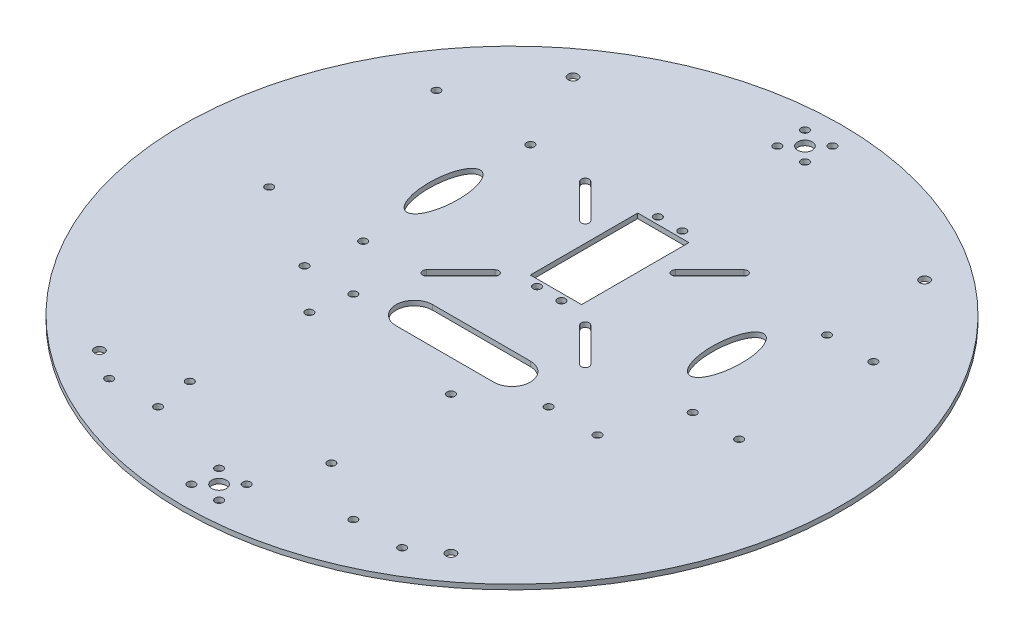
SolidWorks part; units mm, degrees
ref_plane "前视基准面" through (0, 0, 0) normal (0, 0, 1) x (1, 0, 0)
ref_plane "上视基准面" through (0, 0, 0) normal (0, 1, 0) x (1, 0, 0)
ref_plane "右视基准面" through (0, 0, 0) normal (1, 0, 0) x (0, 0, -1)
sketch "草图1" plane through (0, 0, 0) normal (0, 1, 0) x (1, 0, 0)
  line L0 (0, 135) -> (0, -135) construction
  line L1 (-80, 80) -> (80, 80) construction
  line L2 (-80, 80) -> (-80, -80) construction
  line L3 (-80, -80) -> (80, -80) construction
  line L4 (80, 80) -> (80, -80) construction
  line L5 (-80, 80) -> (80, -80) construction
  line L6 (-80, -80) -> (80, 80) construction
  line L7 (-135, 0) -> (135, 0) construction
  line L9 (-30, 60) -> (30, 60) construction
  line L10 (-30, 60) -> (-30, 0) construction
  line L11 (-30, 0) -> (30, 0) construction
  line L12 (30, 60) -> (30, 0) construction
  line L13 (-30, 60) -> (30, 0) construction
  line L14 (-30, 0) -> (30, 60) construction
  circle A0 centre (0, 0) radius 135
  point P17 (0, 0)
  point P19 (0, 30)
  dimension "D1" = 270
  dimension "D2" = 160
  dimension "D3" = 160
  dimension "D5" = 30
  dimension "D6" = 60
  dimension "D7" = 60
extrude "凸台-拉伸1" add sketch "草图1" along normal blind 2
sketch "云台安装孔" plane through (0, 2, 0) normal (0, 1, 0) x (1, 0, 0)
  line L0 (0, 135) -> (0, -135) construction
  line L1 (-135, 0) -> (135, 0) construction
  line L3 (-18.5, 48.5) -> (18.5, 48.5) construction
  line L4 (-18.5, 48.5) -> (-18.5, 11.5) construction
  line L5 (-18.5, 11.5) -> (18.5, 11.5) construction
  line L6 (18.5, 48.5) -> (18.5, 11.5) construction
  line L7 (-18.5, 48.5) -> (18.5, 11.5) construction
  line L8 (-18.5, 11.5) -> (18.5, 48.5) construction
  line L9 (-62.9961, -18.6558) -> (62.9961, -18.6558) construction
  line L10 (-62.9961, -18.6558) -> (-62.9961, -86.2012) construction
  line L11 (-62.9961, -86.2012) -> (62.9961, -86.2012) construction
  line L12 (62.9961, -18.6558) -> (62.9961, -86.2012) construction
  line L13 (-62.9961, -18.6558) -> (62.9961, -86.2012) construction
  line L14 (-62.9961, -86.2012) -> (62.9961, -18.6558) construction
  line L15 (-10.5, 62) -> (10.5, 62)
  line L16 (-10.5, 62) -> (-10.5, 18)
  line L17 (-10.5, 18) -> (10.5, 18)
  line L18 (10.5, 62) -> (10.5, 18)
  line L19 (-10.5, 62) -> (10.5, 18) construction
  line L20 (-10.5, 18) -> (10.5, 62) construction
  line L21 (-5, 64.75) -> (5, 64.75) construction
  line L22 (-5, 64.75) -> (-5, 15.25) construction
  line L23 (-5, 15.25) -> (5, 15.25) construction
  line L24 (5, 64.75) -> (5, 15.25) construction
  line L25 (-5, 64.75) -> (5, 15.25) construction
  line L26 (-5, 15.25) -> (5, 64.75) construction
  line L27 (-38.5, 68.5) -> (38.5, 68.5) construction
  line L28 (-38.5, 68.5) -> (-38.5, -8.5) construction
  line L29 (-38.5, -8.5) -> (38.5, -8.5) construction
  line L30 (38.5, 68.5) -> (38.5, -8.5) construction
  line L31 (-38.5, 68.5) -> (38.5, -8.5) construction
  line L32 (-38.5, -8.5) -> (38.5, 68.5) construction
  circle A0 centre (0, 0) radius 135 construction
  circle A1 centre (-5, 64.75) radius 1.6
  circle A2 centre (5, 64.75) radius 1.6
  circle A3 centre (-5, 15.25) radius 1.6
  circle A4 centre (5, 15.25) radius 1.6
  circle A5 centre (18.5, 48.5) radius 1.6
  circle A6 centre (18.5, 11.5) radius 1.6
  circle A7 centre (-18.5, 11.5) radius 1.6
  circle A8 centre (-18.5, 48.5) radius 1.6
  point P3 (0, 30)
  point P8 (0, 30)
  point P13 (0, -52.4285)
  point P18 (0, 40)
  point P23 (0, 40)
  point P50 (0, 30)
  dimension "D3" = 21
  dimension "D8" = 3.2
  dimension "D9" = 3.2
  dimension "D10" = 3.2
  dimension "D11" = 3.2
  dimension "D12" = 3.2
  dimension "D13" = 3.2
  dimension "D1" = 37
  dimension "D2" = 37
  dimension "D4" = 44
  dimension "D5" = 10
  dimension "D6" = 10
  dimension "D7" = 49.5
  dimension "D14" = 30
  dimension "D15" = 77
  dimension "D16" = 77
extrude "切除-拉伸1" cut sketch "云台安装孔" against normal blind 10
sketch "扩展板安装孔" plane through (0, 2, 0) normal (0, 1, 0) x (1, 0, 0)
  line L0 (0, 135) -> (0, -135) construction
  line L1 (15.5, -40.5) -> (15.5, -89.5) construction
  line L2 (-60, -25) -> (60, -25) construction
  line L3 (-60, -25) -> (-60, -105) construction
  line L4 (-60, -105) -> (60, -105) construction
  line L5 (60, -25) -> (60, -105) construction
  line L6 (-60, -25) -> (60, -105) construction
  line L7 (-60, -105) -> (60, -25) construction
  line L8 (-40, -25) -> (40, -25) construction
  line L9 (-40, -25) -> (-40, -105) construction
  line L10 (-40, -105) -> (40, -105) construction
  line L11 (40, -25) -> (40, -105) construction
  line L12 (-40, -25) -> (40, -105) construction
  line L13 (-40, -105) -> (40, -25) construction
  line L14 (-42.5, -40.5) -> (42.5, -40.5) construction
  line L15 (-42.5, -40.5) -> (-42.5, -89.5) construction
  line L16 (-42.5, -89.5) -> (42.5, -89.5) construction
  line L17 (42.5, -40.5) -> (42.5, -89.5) construction
  line L18 (-42.5, -40.5) -> (42.5, -89.5) construction
  line L19 (-42.5, -89.5) -> (42.5, -40.5) construction
  circle A0 centre (0, 0) radius 135 construction
  circle A1 centre (-60, -25) radius 1.6
  circle A2 centre (-40, -25) radius 1.6
  circle A3 centre (40, -25) radius 1.6
  circle A4 centre (60, -25) radius 1.6
  circle A5 centre (60, -105) radius 1.6
  circle A6 centre (40, -105) radius 1.6
  circle A7 centre (-40, -105) radius 1.6
  circle A8 centre (-60, -105) radius 1.6
  circle A9 centre (-42.5, -89.5) radius 1.6
  circle A12 centre (-42.5, -40.5) radius 1.6
  circle A13 centre (15.5, -40.5) radius 1.6
  circle A14 centre (15.5, -89.5) radius 1.6
  point P5 (0, -65)
  point P10 (0, -65)
  point P15 (0, -65)
  dimension "D7" = 65
  dimension "D1" = 120
  dimension "D2" = 80
  dimension "D3" = 80
  dimension "D4" = 85
  dimension "D5" = 49
  dimension "D6" = 58
extrude "切除-拉伸2" cut sketch "扩展板安装孔" against normal blind 10
sketch "草图4" plane through (0, 2, 0) normal (0, 1, 0) x (1, 0, 0)
  line L0 (0, 135) -> (0, -135) construction
  line L1 (-135, 0) -> (135, 0) construction
  line L2 (-20, -12.5) -> (20, -12.5)
  line L3 (-20, -12.5) -> (-20, -27.5) construction
  line L4 (-20, -27.5) -> (20, -27.5)
  line L5 (20, -12.5) -> (20, -27.5) construction
  line L6 (-20, -12.5) -> (20, -27.5) construction
  line L7 (-20, -27.5) -> (20, -12.5) construction
  line L8 (-72, 97) -> (72, 97) construction
  line L9 (-72, 97) -> (-72, -97) construction
  line L10 (-72, -97) -> (72, -97) construction
  line L11 (72, 97) -> (72, -97) construction
  line L12 (-72, 97) -> (72, -97) construction
  line L13 (-72, -97) -> (72, 97) construction
  circle A0 centre (0, 0) radius 135 construction
  arc A1 (-20, -12.5) -> (-20, -27.5) centre (-20, -20) ccw
  arc A2 (20, -12.5) -> (20, -27.5) centre (20, -20) cw
  circle A3 centre (-72, 97) radius 2
  circle A4 centre (72, 97) radius 2
  circle A5 centre (72, -97) radius 2
  circle A6 centre (-72, -97) radius 2
  circle A7 centre (0, -120) radius 3
  circle A8 centre (0, 120) radius 8 construction
  circle A9 centre (-5.6569, -125.6569) radius 1.6
  circle A10 centre (-5.6569, -114.3431) radius 1.6
  circle A11 centre (5.6569, -114.3431) radius 1.6
  circle A12 centre (5.6569, -125.6569) radius 1.6
  circle A13 centre (5.6569, 125.6569) radius 1.6
  circle A14 centre (5.6569, 114.3431) radius 1.6
  circle A15 centre (-5.6569, 114.3431) radius 1.6
  circle A16 centre (-5.6569, 125.6569) radius 1.6
  circle A17 centre (0, -120) radius 8 construction
  circle A18 centre (0, 120) radius 3
  point P5 (0, -20)
  point P12 (0, 0)
  point P41 (0, -120)
  point P50 (0, 120)
  dimension "D5" = 120
  dimension "D6" = 4
  dimension "D7" = 4
  dimension "D8" = 4
  dimension "D9" = 4
  dimension "D12" = 4
  dimension "D10" = 16
  dimension "D11" = 4
  dimension "D14" = 6
  dimension "D1" = 15
  dimension "D2" = 40
  dimension "D3" = 144
  dimension "D4" = 194
  dimension "D13" = 20
extrude "切除-拉伸3" cut sketch "草图4" against normal blind 10
sketch "草图5" plane through (0, 2, 0) normal (0, 1, 0) x (1, 0, 0)
  line L0 (-31.3686, 63.6314) -> (-17.3686, 49.6314)
  line L1 (-10.5, 62) -> (-10.5, 18) construction
  line L2 (-33.6314, 61.3686) -> (-19.6314, 47.3686)
  line L3 (-32.5, 62.5) -> (32.5, 62.5) construction
  line L4 (-32.5, 62.5) -> (-32.5, -2.5) construction
  line L5 (-32.5, -2.5) -> (32.5, -2.5) construction
  line L6 (32.5, 62.5) -> (32.5, -2.5) construction
  line L7 (-32.5, 62.5) -> (32.5, -2.5) construction
  line L8 (-32.5, -2.5) -> (32.5, 62.5) construction
  line L9 (33.6314, 61.3686) -> (19.6314, 47.3686)
  line L10 (31.3686, 63.6314) -> (17.3686, 49.6314)
  line L11 (31.3686, -3.6314) -> (17.3686, 10.3686)
  line L12 (33.6314, -1.3686) -> (19.6314, 12.6314)
  line L13 (-33.6314, -1.3686) -> (-19.6314, 12.6314)
  line L14 (-31.3686, -3.6314) -> (-17.3686, 10.3686)
  arc A0 (33.6314, 61.3686) -> (31.3686, 63.6314) centre (32.5, 62.5) ccw
  arc A1 (-19.6314, 47.3686) -> (-17.3686, 49.6314) centre (-18.5, 48.5) ccw
  arc A2 (-31.3686, 63.6314) -> (-33.6314, 61.3686) centre (-32.5, 62.5) ccw
  arc A3 (17.3686, 49.6314) -> (19.6314, 47.3686) centre (18.5, 48.5) ccw
  arc A4 (31.3686, -3.6314) -> (33.6314, -1.3686) centre (32.5, -2.5) ccw
  arc A5 (19.6314, 12.6314) -> (17.3686, 10.3686) centre (18.5, 11.5) ccw
  arc A6 (-33.6314, -1.3686) -> (-31.3686, -3.6314) centre (-32.5, -2.5) ccw
  arc A7 (-17.3686, 10.3686) -> (-19.6314, 12.6314) centre (-18.5, 11.5) ccw
  point P5 (0, 30)
  point P35 (0, 30)
  dimension "D4" = 3.2
  dimension "D1" = 30
  dimension "D2" = 10.5
  dimension "D3" = 65
  dimension "D5" = 1.6
  dimension "D6" = 4
extrude "切除-拉伸4" cut sketch "草图5" against normal blind 10
sketch "草图6" plane through (0, 2, 0) normal (0, 1, 0) x (1, 0, 0)
  line L0 (33.6314, -3.6314) -> (33.6314, 63.6314) construction
  line L1 (33.6314, 30) -> (118.3005, 30) construction
  line L2 (0, 120) -> (0, -27.5) construction
  line L3 (-20, -27.5) -> (20, -27.5) construction
  line L4 (-33.6314, -3.6314) -> (-33.6314, 63.6314) construction
  line L5 (71.5372, 2.5) -> (90.5372, 2.5) construction
  line L6 (71.5372, 2.5) -> (71.5372, 57.5) construction
  line L7 (71.5372, 57.5) -> (90.5372, 57.5) construction
  line L8 (90.5372, 2.5) -> (90.5372, 57.5) construction
  line L9 (71.5372, 2.5) -> (90.5372, 57.5) construction
  line L10 (71.5372, 57.5) -> (90.5372, 2.5) construction
  line L11 (-33.6314, 30) -> (-118.3005, 30) construction
  line L14 (-95.216, -4.25) -> (-56.716, -4.25) construction
  line L15 (-95.216, -4.25) -> (-95.216, 64.25) construction
  line L16 (-95.216, 64.25) -> (-56.716, 64.25) construction
  line L17 (-56.716, -4.25) -> (-56.716, 64.25) construction
  line L18 (-95.216, -4.25) -> (-56.716, 64.25) construction
  line L19 (-95.216, 64.25) -> (-56.716, -4.25) construction
  arc A0 (31.3686, -3.6314) -> (33.6314, -1.3686) centre (32.5, -2.5) ccw construction
  arc A1 (33.6314, 61.3686) -> (31.3686, 63.6314) centre (32.5, 62.5) ccw construction
  circle A2 centre (71.5372, 2.5) radius 1.6
  circle A3 centre (90.5372, 2.5) radius 1.6
  circle A4 centre (90.5372, 57.5) radius 1.6
  circle A5 centre (71.5372, 57.5) radius 1.6
  circle A6 centre (-95.216, -4.25) radius 1.6
  circle A7 centre (-56.716, -4.25) radius 1.6
  circle A8 centre (-95.216, 64.25) radius 1.6
  circle A9 centre (-56.716, 64.25) radius 1.6
  ellipse E0 centre (-58.0311, 30) end of major axis (-58.0311, 15) minor radius 6
  ellipse E1 centre (58.0311, 30) end of major axis (58.0311, 45) minor radius 6
  point P15 (81.0372, 30)
  point P49 (-75.966, 30)
  dimension "D3" = 6
  dimension "D7" = 3.2
  dimension "D1" = 19
  dimension "D2" = 55
  dimension "D4" = 15
  dimension "D5" = 38.5
  dimension "D6" = 68.5
extrude "切除-拉伸7" cut sketch "草图6" against normal blind 10 contours A7 | A2 | A3 | A4 | A5 | E0 | E1 | A6 | A8 | A9
